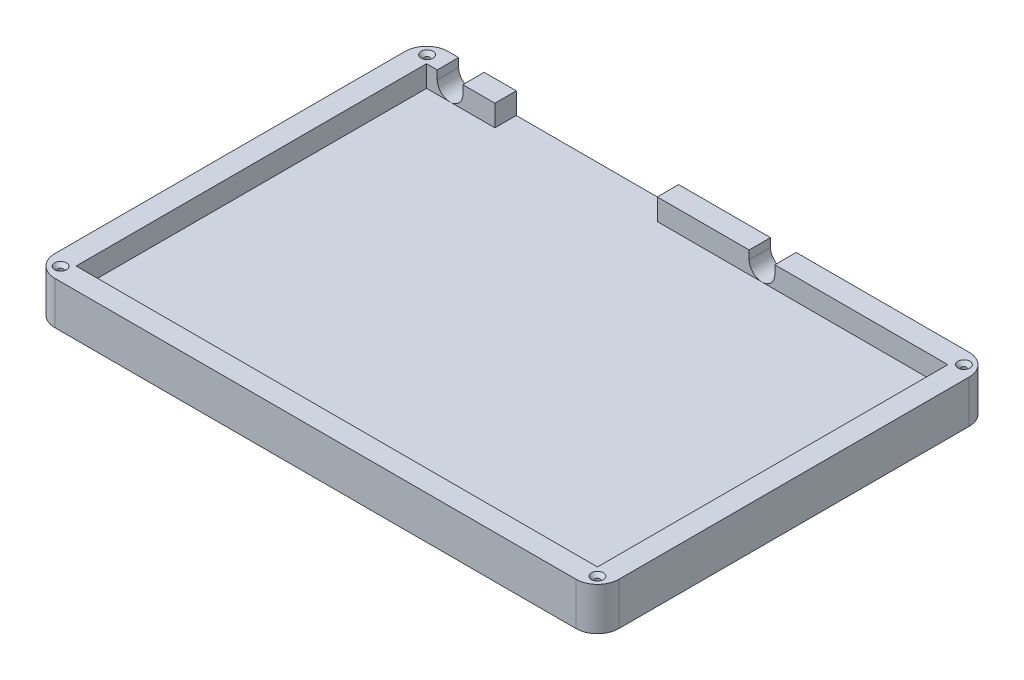
SolidWorks part; units mm, degrees
ref_plane "Front Plane" through (0, 0, 0) normal (0, 0, 1) x (1, 0, 0)
ref_plane "Top Plane" through (0, 0, 0) normal (0, 1, 0) x (1, 0, 0)
ref_plane "Right Plane" through (0, 0, 0) normal (1, 0, 0) x (0, 0, -1)
sketch "Sketch2" plane through (0, 0, 0) normal (0, 1, 0) x (1, 0, 0)
  line L0 (-61, 41) -> (61, 41)
  line L1 (-61, -46) -> (61, -46)
  line L2 (-66, -41) -> (-66, 41)
  line L3 (-61, 46) -> (61, 46)
  line L4 (66, -41) -> (66, 41)
  line L5 (-66, -46) -> (66, 46) construction
  line L6 (-66, 46) -> (66, -46) construction
  line L7 (61, -41) -> (61, 41)
  line L8 (-61, -41) -> (61, -41)
  line L9 (-61, -41) -> (-61, 41)
  arc A0 (-61, -46) -> (-66, -41) centre (-61, -41) cw
  arc A1 (61, -46) -> (66, -41) centre (61, -41) ccw
  arc A2 (61, 46) -> (66, 41) centre (61, 41) cw
  arc A3 (-66, 41) -> (-61, 46) centre (-61, 41) cw
  arc A4 (61, 41) -> (61, 41) centre (61, 41) cw
  arc A5 (61, -41) -> (61, -41) centre (61, -41) ccw
  arc A6 (-61, -41) -> (-61, -41) centre (-61, -41) cw
  arc A7 (-61, 41) -> (-61, 41) centre (-61, 41) cw
  point P0 (0, 0)
  dimension "D3" = 5
  dimension "D1" = 92
  dimension "D2" = 132
  dimension "D4" = 5
extrude "Boss-Extrude1" add sketch "Sketch2" along normal blind 5 contours L9 L8 L7 L0 | A3 L2 A0 L1 A1 L4 A2 L3 L8 L9 L0 L7 region at (0, 0, 0) region at (-63.3978, 0, 43.3978)
extrude "Boss-Extrude2" add sketch "Sketch2<3>" along normal blind 10
sketch "Sketch2<3>" plane through (0, 0, 0) normal (0, 1, 0) x (1, 0, 0) same geometry as "Sketch2"
hole_wizard "#0-80 Tapped Hole1" positions "3DSketch5" profile "Sketch7" tap size "#0-80" standard "ANSI Inch"
sketch3d "3DSketch5"
  point P0 (62.88, 10, -42.8891)
  point P2 (62.88, 10, 42.8803)
  point P4 (-62.7584, 10, -42.8891)
  point P6 (-62.7584, 10, 42.8803)
  point P9 (-54.7922, 10, 42.8803)
  point P10 (0, 0, 0)
  point P11 (-62.7584, 10, 42.8803)
  point P12 (0, 0, 0)
  point P13 (-62.7584, 10, -42.8891)
  point P14 (62.88, 10, -42.8891)
  point P15 (62.88, 10, 42.8803)
sketch "Sketch7" plane through (62.88, 10, -42.8891) normal (1, 0, 0) x (0, 0, 1)
  line L0 (0, 0) -> (0, 4)
  line L1 (0, 4) -> (0.5956, 3.6421)
  line L2 (0.5956, 3.6421) -> (0.5956, 0.8014)
  line L3 (0.5956, 0.8014) -> (1.397, 0)
  line L5 (1.397, 0) -> (0, 0)
  line L6 (-0.5956, 0.8014) -> (-1.397, 0) construction
  line L10 (0, 4) -> (-0.5956, 3.6421) construction
  line L11 (0, -6.35) -> (0, 107.95) construction
  dimension "Tap Drill Dia." = 1.1913
  dimension "Tap Drill Depth" = 4
  dimension "Near C'Sink Dia." = 2.794
  dimension "Near C'Sink Angle" = 90
  dimension "Drill Angle" = 118
sketch "Sketch8" plane through (0, 10, 0) normal (0, 1, 0) x (1, 0, 0)
  line L0 (61, 46) -> (-61, 46) construction
  line L1 (-45, 46) -> (-7, 46)
  line L2 (-45, 46) -> (-45, 41)
  line L3 (-45, 41) -> (-7, 41)
  line L4 (-7, 46) -> (-7, 41)
  line L5 (61, 41) -> (-61, 41) construction
  dimension "D1" = 38
  dimension "D2" = 16
extrude "Cut-Extrude1" cut sketch "Sketch8" against normal up to surface (5 mm away) up to face at (0, 5, 0)
sketch "Sketch9" plane through (0, 0, -46) normal (0, 0, -1) x (-1, 0, 0)
  line L0 (-20.5, 10) -> (-20.5, 8)
  line L1 (-61, 10) -> (7, 10) construction
  line L2 (-14.5, 8) -> (-14.5, 10)
  line L3 (-20.5, 10) -> (-14.5, 10)
  arc A0 (-20.5, 8) -> (-14.5, 8) centre (-17.5, 8) ccw
  point P6 (-17.5, 10)
  dimension "D1" = 3
  dimension "D2" = 2
  dimension "D3" = 43.5
extrude "Cut-Extrude2" cut sketch "Sketch9" against normal up to surface (5 mm away) up to face at (27, 7.5, -41)
sketch "Sketch10" plane through (0, 0, -46) normal (0, 0, -1) x (-1, 0, 0)
  line L0 (52.5, 10) -> (52.5, 8)
  line L1 (45, 10) -> (61, 10) construction
  line L2 (58.5, 8) -> (58.5, 10)
  line L3 (58.5, 10) -> (52.5, 10)
  arc A0 (52.5, 8) -> (58.5, 8) centre (55.5, 8) ccw
  dimension "D2" = 3
  dimension "D1" = 2
  dimension "D3" = 2.5
extrude "Cut-Extrude3" cut sketch "Sketch10" against normal up to surface (5 mm away) up to face at (-53, 7.5, -41)
